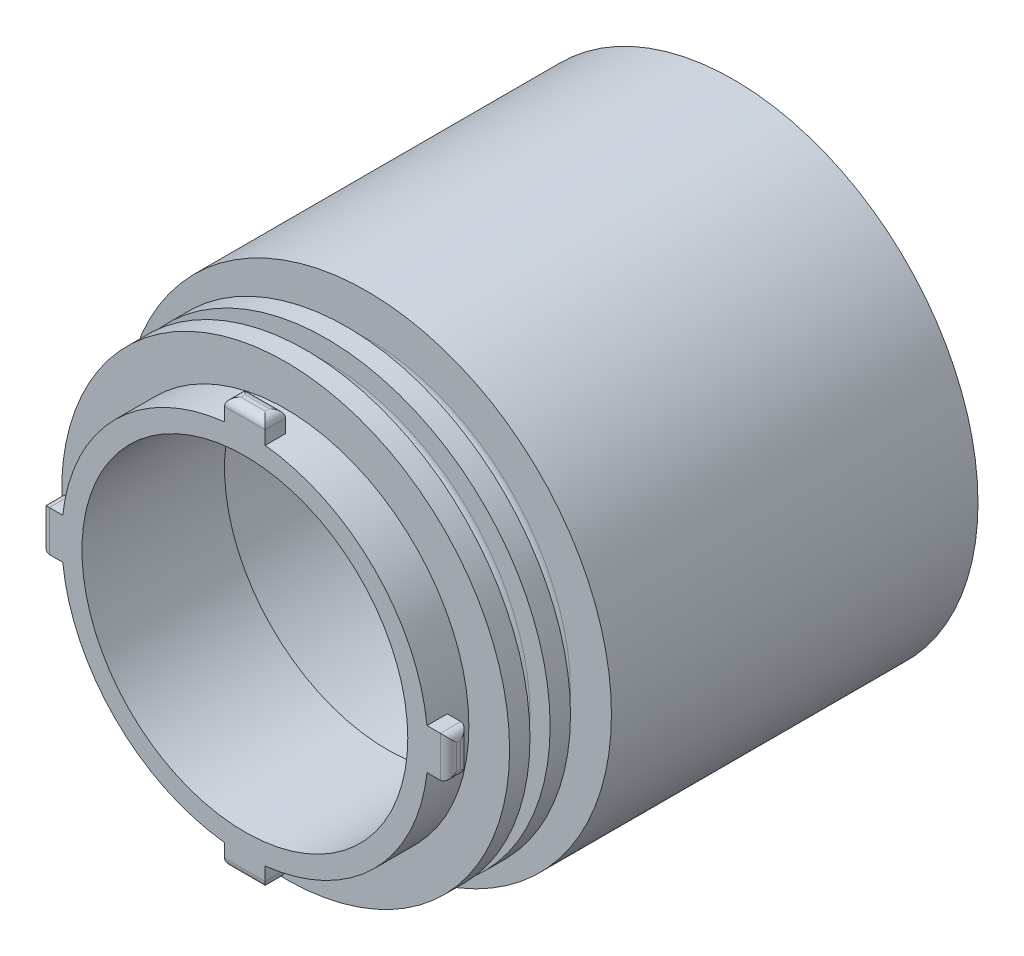
SolidWorks part; units mm, degrees
ref_plane "Front Plane" through (0, 0, 0) normal (1, 0, 0) x (0, 1, 0)
ref_plane "Top Plane" through (0, 0, 0) normal (0, 0, 1) x (0, 1, 0)
ref_plane "Right Plane" through (0, 0, 0) normal (0, 1, 0) x (-1, 0, 0)
sketch "Sketch2" plane through (0, 0, 0) normal (1, 0, 0) x (0, 1, 0)
  line L8 (0, 44.4039) -> (0, -174.5694) construction
  line L15 (-76.2, -119.3597) -> (-76.2, -5.0597)
  line L18 (-76.2, -5.0597) -> (-63.4357, -5.0597)
  line L21 (-69.7857, 1.2903) -> (-69.7857, 7.6403)
  line L24 (-63.5, 13.9903) -> (-69.85, 13.9903)
  line L25 (-69.85, 13.9903) -> (-69.85, 20.3403)
  line L29 (-57.15, 20.3403) -> (-57.15, 33.0403)
  line L30 (-57.15, 33.0403) -> (-50.8, 33.0403)
  line L33 (-63.5, -11.4097) -> (-50.8, -11.4097)
  line L34 (-50.8, -11.4097) -> (-50.8, 33.0403)
  line L36 (-69.7857, 1.2903) -> (-63.4357, 1.2903)
  line L37 (-69.85, 20.3403) -> (-57.15, 20.3403)
  line L38 (-69.7857, 7.6403) -> (-63.5, 7.6403)
  line L39 (-76.2, -119.3597) -> (-69.7857, -119.3597)
  line L40 (-69.7857, -119.3597) -> (-69.7857, -81.2597)
  line L41 (-69.7857, -81.2597) -> (-63.5, -81.2597)
  line L42 (-63.5, -81.2597) -> (-63.5, -11.4097)
  arc A0 (-63.5, 13.9903) -> (-63.5, 7.6403) centre (-63.5, 10.8153) cw
  arc A2 (-63.4357, 1.2903) -> (-63.4357, -5.0597) centre (-63.4357, -1.8847) cw
  dimension "D2" = 50.8
  dimension "D3" = 6.35
  dimension "D4" = 6.35
  dimension "D5" = 38.1
  dimension "D6" = 6.35
  dimension "D7" = 76.2
  dimension "D8" = 6.35
  dimension "D9" = 12.7
  dimension "D10" = 6.35
  dimension "D11" = 6.35
  dimension "D13" = 12.7
revolve "Revolve1" add sketch "Sketch2" angle 360 about L8
sketch "Sketch3" plane through (0, 0, 0) normal (1, 0, 0) x (0, 1, 0)
  line L0 (0, -5.3298) -> (0, 40.8214) construction
  line L7 (50.8, 33.0403) -> (-50.8, 33.0403) construction
  line L8 (-6.35, 33.0403) -> (6.35, 33.0403)
  line L9 (-6.35, 33.0403) -> (-6.35, 26.6903)
  line L10 (-6.35, 26.6903) -> (6.35, 26.6903)
  line L11 (6.35, 33.0403) -> (6.35, 26.6903)
  dimension "D1" = 6.35
  dimension "D2" = 6.35
  dimension "D3" = 6.35
extrude "Boss-Extrude1" add sketch "Sketch3" along normal blind 63.5 and the other way blind 63.5
sketch "Sketch4" plane through (0, 0, 0) normal (0, 1, 0) x (-1, 0, 0)
  line L0 (0, -5.6154) -> (0, 40.65) construction
  line L7 (56.7961, 33.0403) -> (-56.7961, 33.0403) construction
  line L8 (-6.35, 33.0403) -> (6.35, 33.0403)
  line L9 (-6.35, 33.0403) -> (-6.35, 26.6903)
  line L10 (-6.35, 26.6903) -> (6.35, 26.6903)
  line L11 (6.35, 33.0403) -> (6.35, 26.6903)
  dimension "D1" = 6.35
  dimension "D2" = 6.35
  dimension "D3" = 6.35
extrude "Boss-Extrude2" add sketch "Sketch4" along normal blind 63.5 and the other way blind 63.5
sketch "Sketch5" plane through (0, 0, 0) normal (0, 0, 1) x (0, 1, 0)
  circle A0 centre (0, 0) radius 50.8
  dimension "D1" = 101.6
extrude "Cut-Extrude2" cut sketch "Sketch5" against normal through all both and the other way through all
fillet "Fillet1" radius 2.54 16 edges at (63.5, 0, 33.0403) (63.5, 6.35, 29.8653) (63.5, 0, 26.6903) (63.5, -6.35, 29.8653) (0, -63.5, 26.6903) (0, -63.5, 33.0403) (-63.5, 0, 26.6903) (-63.5, 0, 33.0403) (0, 63.5, 26.6903) (0, 63.5, 33.0403) (6.35, 63.5, 29.8653) (-6.35, 63.5, 29.8653) (-63.5, -6.35, 29.8653) (-63.5, 6.35, 29.8653) (-6.35, -63.5, 29.8653) (6.35, -63.5, 29.8653)
